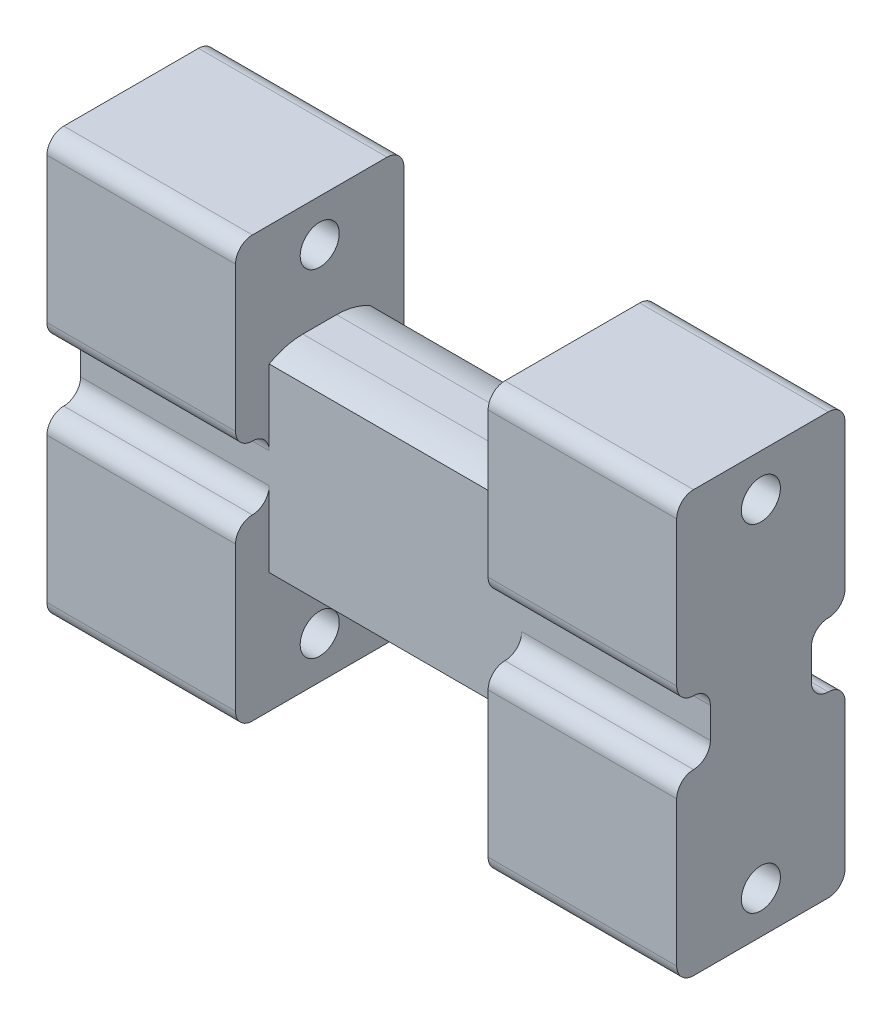
SolidWorks part; units mm, degrees
material "ABS"
ref_plane "Front Plane" through (0, 0, 0) normal (0, 0, 1) x (1, 0, 0)
ref_plane "Top Plane" through (0, 0, 0) normal (0, 1, 0) x (1, 0, 0)
ref_plane "Right Plane" through (0, 0, 0) normal (1, 0, 0) x (0, 0, -1)
sketch "Sketch1" plane through (0, 0, 0) normal (0, 1, 0) x (1, 0, 0)
  line L1 (0, 0) -> (47.498, 0)
  line L2 (0, 0) -> (0, 12.7)
  line L3 (0, 12.7) -> (47.498, 12.7)
  line L4 (47.498, 0) -> (47.498, 12.7)
  dimension "D1" = 47.498
  dimension "D2" = 12.7
extrude "Boss-Extrude1" add sketch "Sketch1" along normal blind 31.75
sketch "Sketch2" plane through (0, 0, 0) normal (-1, 0, 0) x (0, 0, 1)
  line L11 (-6.35, 3.175) -> (-6.35, 28.575) construction
  line L12 (-12.7, 31.75) -> (-12.7, 0) construction
  line L13 (-12.7, 31.75) -> (0, 31.75) construction
  circle A0 centre (-6.35, 3.175) radius 1.4732
  circle A1 centre (-6.35, 28.575) radius 1.4732
  point P6 (-12.7, 15.875)
  point P9 (-6.35, 15.875)
  point P12 (-6.35, 31.75)
  dimension "D1" = 2.9464
  dimension "D2" = 2.9464
  dimension "D3" = 25.4
extrude "Cut-Extrude1" cut sketch "Sketch2" against normal blind 47.498
sketch "Sketch3" plane through (0, 0, -12.7) normal (0, 0, -1) x (-1, 0, 0)
  line L0 (6.985, 0) -> (-6.985, 0) construction
  line L1 (-33.274, 0) -> (-14.224, 0)
  line L2 (-33.274, 0) -> (-33.274, 8.382)
  line L3 (-33.274, 8.382) -> (-14.224, 8.382)
  line L4 (-14.224, 0) -> (-14.224, 8.382)
  line L5 (-47.498, 31.75) -> (0, 31.75) construction
  line L6 (-33.274, 31.75) -> (-14.224, 31.75)
  line L7 (-33.274, 31.75) -> (-33.274, 23.368)
  line L8 (-33.274, 23.368) -> (-14.224, 23.368)
  line L9 (-14.224, 31.75) -> (-14.224, 23.368)
  line L11 (-47.498, 0) -> (0, 0) construction
  point P14 (-23.749, 0)
  point P15 (-23.749, 8.382)
  dimension "D1" = 8.382
  dimension "D2" = 8.382
  dimension "D3" = 19.05
extrude "Cut-Extrude2" cut sketch "Sketch3" against normal blind 47.498
fillet "Fillet1" radius 5.08 4 edges at (23.749, 8.382, 0) (23.749, 8.382, -12.7) (23.749, 23.368, 0) (23.749, 23.368, -12.7)
sketch "Sketch4" plane through (0, 0, 0) normal (0, 0, 1) x (1, 0, 0)
  line L0 (0, 31.75) -> (0, 0) construction
  line L1 (0, 13.462) -> (47.498, 13.462)
  line L2 (0, 13.462) -> (0, 18.288)
  line L3 (0, 18.288) -> (47.498, 18.288)
  line L4 (47.498, 13.462) -> (47.498, 18.288)
  line L5 (47.498, 31.75) -> (47.498, 0) construction
  line L6 (33.274, 18.288) -> (14.224, 18.288) construction
  line L7 (14.224, 13.462) -> (33.274, 13.462) construction
extrude "Cut-Extrude3" cut sketch "Sketch4" against normal blind 2.54
sketch "Sketch5" plane through (0, 0, -12.7) normal (0, 0, -1) x (-1, 0, 0)
  line L0 (-47.498, 13.462) -> (0, 13.462)
  line L1 (-47.498, 13.462) -> (-47.498, 18.288)
  line L2 (-47.498, 18.288) -> (0, 18.288)
  line L3 (0, 13.462) -> (0, 18.288)
  line L4 (-14.224, 18.288) -> (-33.274, 18.288) construction
  line L5 (0, 31.75) -> (0, 0) construction
  line L6 (-47.498, 31.75) -> (-47.498, 0) construction
  line L7 (-33.274, 13.462) -> (-14.224, 13.462) construction
extrude "Cut-Extrude4" cut sketch "Sketch5" against normal blind 2.54
sketch "Sketch6" plane through (0, 0, 0) normal (0, 0, 1) x (1, 0, 0)
  line L0 (14.224, 18.288) -> (14.224, 31.75) construction
  line L1 (14.224, 27.432) -> (33.274, 27.432)
  line L2 (14.224, 27.432) -> (14.224, 8.382)
  line L3 (14.224, 8.382) -> (33.274, 8.382)
  line L4 (33.274, 27.432) -> (33.274, 8.382)
  line L5 (14.224, 18.288) -> (14.224, 23.368) construction
extrude "Cut-Extrude5" cut sketch "Sketch6" against normal blind 2.54
sketch "Sketch7" plane through (0, 0, -12.7) normal (0, 0, -1) x (-1, 0, 0)
  line L0 (-33.274, 31.75) -> (-33.274, 18.288) construction
  line L1 (-33.274, 25.3881) -> (-14.224, 25.3881)
  line L2 (-33.274, 25.3881) -> (-33.274, 8.382)
  line L3 (-33.274, 8.382) -> (-14.224, 8.382)
  line L4 (-14.224, 25.3881) -> (-14.224, 8.382)
extrude "Cut-Extrude6" cut sketch "Sketch7" against normal blind 2.54
fillet "Fillet2" radius 1.27 24 edges at (40.386, 13.462, 0) (40.386, 13.462, -2.54) (40.386, 18.288, -2.54) (40.386, 18.288, 0) (7.112, 13.462, 0) (7.112, 13.462, -2.54) (7.112, 18.288, -2.54) (7.112, 18.288, 0) (7.112, 31.75, 0) (40.386, 31.75, 0) (7.112, 0, 0) (40.386, 0, 0) (40.386, 0, -12.7) (40.386, 31.75, -12.7) (40.386, 13.462, -12.7) (40.386, 13.462, -10.16) (40.386, 18.288, -10.16) (40.386, 18.288, -12.7) (7.112, 31.75, -12.7) (7.112, 18.288, -10.16) (7.112, 18.288, -12.7) (7.112, 0, -12.7) (7.112, 13.462, -12.7) (7.112, 13.462, -10.16)
